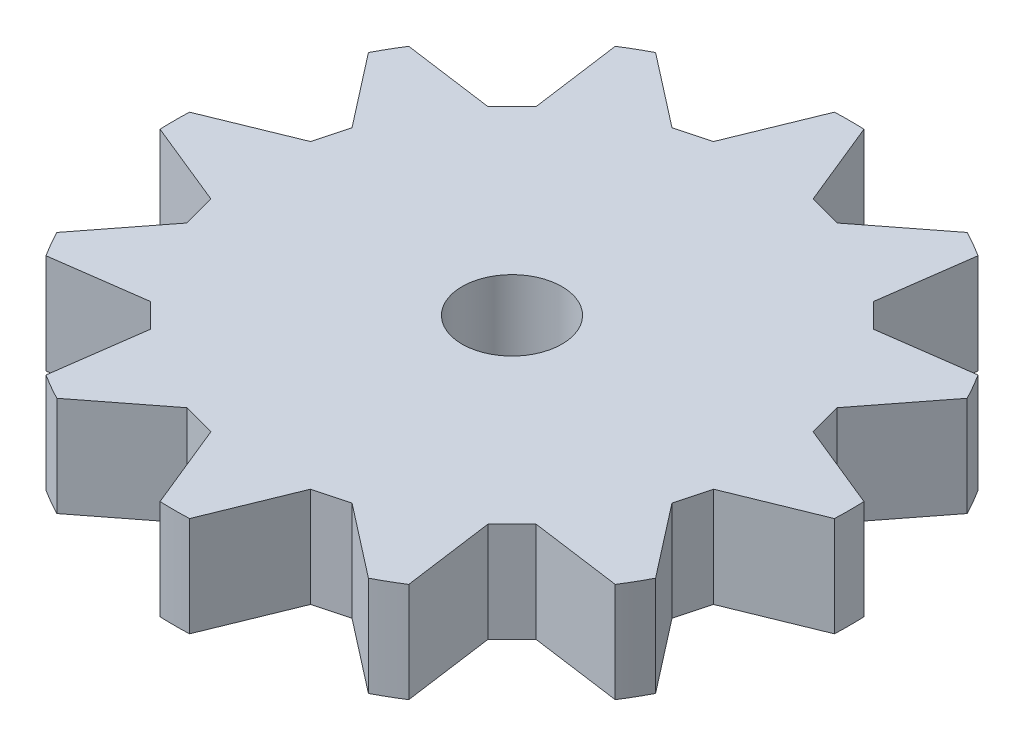
SolidWorks part; units mm, degrees
ref_plane "Front Plane" through (0, 0, 0) normal (0, 0, 1) x (1, 0, 0)
ref_plane "Top Plane" through (0, 0, 0) normal (0, 1, 0) x (1, 0, 0)
ref_plane "Right Plane" through (0, 0, 0) normal (1, 0, 0) x (0, 0, -1)
sketch "Sketch1" plane through (0, 0, 0) normal (0, 1, 0) x (1, 0, 0)
  circle A0 centre (0, 0) radius 15
  circle A1 centre (0, 0) radius 2.5
  dimension "D1" = 30
  dimension "D2" = 5
extrude "Boss-Extrude1" add sketch "Sketch1" along normal blind 5
sketch "Sketch2" plane through (0, 5, 0) normal (0, 1, 0) x (1, 0, 0)
  circle A3 centre (0, 0) radius 17
  circle A5 centre (0, 0) radius 15 construction
  circle M12 centre (0, 0) radius 2.5
  dimension "D1" = 2
extrude "Boss-Extrude2" add sketch "Sketch2" against normal up to surface (5 mm away) contours M12 | A3 region at (0, 5, 0) up to face at (0, 0, 15)
sketch "Sketch3" plane through (0, 5, 0) normal (0, 1, 0) x (1, 0, 0)
  line L0 (0, 0) -> (0, 17) construction
  line L1 (0.8001, 17) -> (-0.8001, 17)
  line L2 (-0.8001, 17) -> (-2.5659, 12.6675)
  line L3 (-2.5659, 12.6675) -> (-3.3388, 12.4604)
  line L4 (-9.6038, 14.0274) -> (6.2988, 15.79) construction
  line L5 (-1.8728, 16.8965) -> (-1.4211, 12.8215) construction
  line L6 (-3.3388, 12.4604) -> (0, 0) construction
  line L7 (2.5659, 12.6675) -> (3.3388, 12.4604)
  line L8 (0.8001, 17) -> (2.5659, 12.6675)
  line L9 (-0.8001, 17) -> (-0.8001, 18) construction
  line L10 (-0.8001, 18) -> (0, 18) construction
  line L11 (0, 18) -> (0, 17) construction
  line L12 (4.1116, 12.2534) -> (3.3388, 12.4604)
  line L13 (7.8071, 15.1225) -> (4.1116, 12.2534)
  line L14 (9.1929, 14.3224) -> (7.8071, 15.1225)
  line L15 (9.1929, 14.3224) -> (8.5559, 9.6874)
  line L16 (8.5559, 9.6874) -> (9.1217, 9.1217)
  line L17 (9.6874, 8.5559) -> (9.1217, 9.1217)
  line L18 (14.3224, 9.1929) -> (9.6874, 8.5559)
  line L19 (15.1225, 7.8071) -> (14.3224, 9.1929)
  line L20 (15.1225, 7.8071) -> (12.2534, 4.1116)
  line L21 (12.2534, 4.1116) -> (12.4604, 3.3388)
  line L22 (12.6675, 2.5659) -> (12.4604, 3.3388)
  line L23 (17, 0.8001) -> (12.6675, 2.5659)
  line L24 (17, -0.8001) -> (17, 0.8001)
  line L25 (17, -0.8001) -> (12.6675, -2.5659)
  line L26 (12.6675, -2.5659) -> (12.4604, -3.3388)
  line L27 (12.2534, -4.1116) -> (12.4604, -3.3388)
  line L28 (15.1225, -7.8071) -> (12.2534, -4.1116)
  line L29 (14.3224, -9.1929) -> (15.1225, -7.8071)
  line L30 (14.3224, -9.1929) -> (9.6874, -8.5559)
  line L31 (9.6874, -8.5559) -> (9.1217, -9.1217)
  line L32 (8.5559, -9.6874) -> (9.1217, -9.1217)
  line L33 (9.1929, -14.3224) -> (8.5559, -9.6874)
  line L34 (7.8071, -15.1225) -> (9.1929, -14.3224)
  line L35 (7.8071, -15.1225) -> (4.1116, -12.2534)
  line L36 (4.1116, -12.2534) -> (3.3388, -12.4604)
  line L37 (2.5659, -12.6675) -> (3.3388, -12.4604)
  line L38 (0.8001, -17) -> (2.5659, -12.6675)
  line L39 (-0.8001, -17) -> (0.8001, -17)
  line L40 (-0.8001, -17) -> (-2.5659, -12.6675)
  line L41 (-2.5659, -12.6675) -> (-3.3388, -12.4604)
  line L42 (-4.1116, -12.2534) -> (-3.3388, -12.4604)
  line L43 (-7.8071, -15.1225) -> (-4.1116, -12.2534)
  line L44 (-9.1929, -14.3224) -> (-7.8071, -15.1225)
  line L45 (-9.1929, -14.3224) -> (-8.5559, -9.6874)
  line L46 (-8.5559, -9.6874) -> (-9.1217, -9.1217)
  line L47 (-9.6874, -8.5559) -> (-9.1217, -9.1217)
  line L48 (-14.3224, -9.1929) -> (-9.6874, -8.5559)
  line L49 (-15.1225, -7.8071) -> (-14.3224, -9.1929)
  line L50 (-15.1225, -7.8071) -> (-12.2534, -4.1116)
  line L51 (-12.2534, -4.1116) -> (-12.4604, -3.3388)
  line L52 (-12.6675, -2.5659) -> (-12.4604, -3.3388)
  line L53 (-17, -0.8001) -> (-12.6675, -2.5659)
  line L54 (-17, 0.8001) -> (-17, -0.8001)
  line L55 (-17, 0.8001) -> (-12.6675, 2.5659)
  line L56 (-12.6675, 2.5659) -> (-12.4604, 3.3388)
  line L57 (-12.2534, 4.1116) -> (-12.4604, 3.3388)
  line L58 (-15.1225, 7.8071) -> (-12.2534, 4.1116)
  line L59 (-14.3224, 9.1929) -> (-15.1225, 7.8071)
  line L60 (-14.3224, 9.1929) -> (-9.6874, 8.5559)
  line L61 (-9.6874, 8.5559) -> (-9.1217, 9.1217)
  line L62 (-8.5559, 9.6874) -> (-9.1217, 9.1217)
  line L63 (-9.1929, 14.3224) -> (-8.5559, 9.6874)
  line L64 (-7.8071, 15.1225) -> (-9.1929, 14.3224)
  line L65 (-7.8071, 15.1225) -> (-4.1116, 12.2534)
  line L66 (-4.1116, 12.2534) -> (-3.3388, 12.4604)
  circle A0 centre (0, 0) radius 17 construction
  circle A1 centre (0, 0) radius 12.9 construction
  circle A2 centre (0, 0) radius 15 construction
  circle A3 centre (0, 0) radius 18
  point P12 (-1.6525, 14.9087)
  point P18 (0, 0)
  point P90 (0, 0)
  circle M14 centre (0, 0) radius 17
  dimension "D1" = 2
  dimension "D2" = 28.5
  dimension "2" = 2.1
  dimension "D3" = 15
  dimension "D4" = 1
  dimension "D5" = 12
extrude "Cut-Extrude1" cut sketch "Sketch3" along direction (0, 1, 0) on the side against the normal up to surface (5 mm away) contours L65 L66 L3 L2 M14 | L13 L8 L7 L12 M14 | L18 L15 L16 L17 M14 | L23 L20 L21 L22 M14 | L28 L25 L26 L27 M14 | L33 L30 L31 L32 M14 | L38 L35 L36 L37 M14 | L43 L40 L41 L42 M14 | L48 L45 L46 L47 M14 | L53 L50 L51 L52 M14 | L58 L55 L56 L57 M14 | L63 L60 L61 L62 M14 | A3 L64 L65 L2 L1 L8 L13 L14 L15 L18 L19 L20 L23 L24 L25 L28 L29 L30 L33 L34 L35 L38 L39 L40 L43 L44 L45 L48 L49 L50 L53 M14 region at (3.9641, 5, -14.7944) region at (-3.9641, 5, -14.7944) region at (10.8302, 5, -10.8302) region at (-10.8302, 5, -10.8302) region at (14.7944, 5, -3.9641) region at (-14.7944, 5, -3.9641) region at (14.7944, 5, 3.9641) region at (-14.7944, 5, 3.9641) region at (10.8302, 5, 10.8302) region at (-10.8302, 5, 10.8302) region at (3.9641, 5, 14.7944) region at (-3.9641, 5, 14.7944) region at (-17.4909, 5, 0) up to face at (0, 0, 2.5)
sketch "Sketch4" plane through (0, 5, 0) normal (0, 1, 0) x (1, 0, 0)
  line L41 (2.4921, 12.5838) -> (4.1337, 12.1439)
  line L42 (4.1337, 12.1439) -> (7.8015, 14.9915)
  line L43 (9.0823, 14.2521) -> (8.4501, 9.6518)
  line L44 (8.4501, 9.6518) -> (9.6518, 8.4501)
  line L45 (9.6518, 8.4501) -> (14.2521, 9.0823)
  line L46 (-7.852, 15.0308) -> (-4.1337, 12.1439)
  line L47 (2.4921, 12.5838) -> (4.0857, 12.1568)
  line L48 (0.7394, 16.8838) -> (2.4921, 12.5838)
  line L49 (-2.4921, 12.5838) -> (-0.7394, 16.8838)
  line L50 (-4.1337, 12.1439) -> (-2.4921, 12.5838)
  line L51 (-7.852, 15.0308) -> (-4.1337, 12.1439) construction
  line L52 (2.4921, 12.5838) -> (4.0857, 12.1568) construction
  line L53 (0.7394, 16.8838) -> (2.4921, 12.5838)
  line L54 (-2.4921, 12.5838) -> (-0.7394, 16.8838)
  line L55 (-4.1337, 12.1439) -> (-2.4921, 12.5838)
  line L56 (14.9915, 7.8015) -> (12.1439, 4.1337)
  line L57 (12.1439, 4.1337) -> (12.5838, 2.4921)
  line L58 (12.5838, 2.4921) -> (16.8838, 0.7394)
  line L59 (16.8838, -0.7394) -> (12.5838, -2.4921)
  line L60 (12.5838, -2.4921) -> (12.1439, -4.1337)
  line L61 (12.1439, -4.1337) -> (14.9915, -7.8015)
  line L62 (14.2521, -9.0823) -> (9.6518, -8.4501)
  line L63 (9.6518, -8.4501) -> (8.4501, -9.6518)
  line L64 (8.4501, -9.6518) -> (9.0823, -14.2521)
  line L65 (7.8015, -14.9915) -> (4.1337, -12.1439)
  line L66 (4.1337, -12.1439) -> (2.4921, -12.5838)
  line L67 (2.4921, -12.5838) -> (0.7394, -16.8838)
  line L68 (-0.7394, -16.8838) -> (-2.4921, -12.5838)
  line L69 (-2.4921, -12.5838) -> (-4.1337, -12.1439)
  line L70 (-4.1337, -12.1439) -> (-7.8015, -14.9915)
  line L71 (-9.0823, -14.2521) -> (-8.4501, -9.6518)
  line L72 (-8.4501, -9.6518) -> (-9.6518, -8.4501)
  line L73 (-9.6518, -8.4501) -> (-14.2521, -9.0823)
  line L74 (-14.9915, -7.8015) -> (-12.1439, -4.1337)
  line L75 (-12.1439, -4.1337) -> (-12.5838, -2.4921)
  line L76 (-12.5838, -2.4921) -> (-16.8838, -0.7394)
  line L77 (-16.8838, 0.7394) -> (-12.5838, 2.4921)
  line L78 (-12.5838, 2.4921) -> (-12.1439, 4.1337)
  line L79 (-12.1439, 4.1337) -> (-14.9915, 7.8015)
  line L80 (-14.2521, 9.0823) -> (-9.6518, 8.4501)
  line L81 (-9.6518, 8.4501) -> (-8.4501, 9.6518)
  line L82 (-8.4501, 9.6518) -> (-9.0823, 14.2521)
  line L83 (-7.8015, 14.9915) -> (-4.1337, 12.1439)
  arc A8 (9.0823, 14.2521) -> (7.8015, 14.9915) centre (0, 0) ccw
  arc A9 (0.7394, 16.8838) -> (-0.7394, 16.8838) centre (0, 0) ccw
  arc A10 (0.7394, 16.8838) -> (-0.7394, 16.8838) centre (0, 0) ccw
  arc A11 (14.9915, 7.8015) -> (14.2521, 9.0823) centre (0, 0) ccw
  arc A12 (16.8838, -0.7394) -> (16.8838, 0.7394) centre (0, 0) ccw
  arc A13 (14.2521, -9.0823) -> (14.9915, -7.8015) centre (0, 0) ccw
  arc A14 (7.8015, -14.9915) -> (9.0823, -14.2521) centre (0, 0) ccw
  arc A15 (-0.7394, -16.8838) -> (0.7394, -16.8838) centre (0, 0) ccw
  arc A16 (-9.0823, -14.2521) -> (-7.8015, -14.9915) centre (0, 0) ccw
  arc A17 (-14.9915, -7.8015) -> (-14.2521, -9.0823) centre (0, 0) ccw
  arc A18 (-16.8838, 0.7394) -> (-16.8838, -0.7394) centre (0, 0) ccw
  arc A19 (-14.2521, 9.0823) -> (-14.9915, 7.8015) centre (0, 0) ccw
  arc A20 (-7.8015, 14.9915) -> (-9.0823, 14.2521) centre (0, 0) ccw
  circle A21 centre (0, 0) radius 18.3542
  point P57 (0, 0)
  arc M8 (-7.7907, 15.1098) -> (-9.1901, 14.3018) centre (0, 0) ccw
  line M9 (-9.1901, 14.3018) -> (-8.5559, 9.6874)
  line M10 (-8.5559, 9.6874) -> (-9.6874, 8.5559)
  line M11 (-9.6874, 8.5559) -> (-14.3018, 9.1901)
  arc M12 (-14.3018, 9.1901) -> (-15.1098, 7.7907) centre (0, 0) ccw
  line M13 (-15.1098, 7.7907) -> (-12.2534, 4.1116)
  line M14 (-12.2534, 4.1116) -> (-12.6675, 2.5659)
  line M15 (-12.6675, 2.5659) -> (-16.9808, 0.8079)
  arc M16 (-16.9808, 0.8079) -> (-16.9808, -0.8079) centre (0, 0) ccw
  line M17 (-16.9808, -0.8079) -> (-12.6675, -2.5659)
  line M18 (-12.6675, -2.5659) -> (-12.2534, -4.1116)
  line M19 (-12.2534, -4.1116) -> (-15.1098, -7.7907)
  arc M20 (-15.1098, -7.7907) -> (-14.3018, -9.1901) centre (0, 0) ccw
  line M21 (-14.3018, -9.1901) -> (-9.6874, -8.5559)
  line M22 (-9.6874, -8.5559) -> (-8.5559, -9.6874)
  line M23 (-8.5559, -9.6874) -> (-9.1901, -14.3018)
  arc M24 (-9.1901, -14.3018) -> (-7.7907, -15.1098) centre (0, 0) ccw
  line M25 (-7.7907, -15.1098) -> (-4.1116, -12.2534)
  line M26 (-4.1116, -12.2534) -> (-2.5659, -12.6675)
  line M27 (-2.5659, -12.6675) -> (-0.8079, -16.9808)
  arc M28 (-0.8079, -16.9808) -> (0.8079, -16.9808) centre (0, 0) ccw
  line M29 (0.8079, -16.9808) -> (2.5659, -12.6675)
  line M30 (2.5659, -12.6675) -> (4.1116, -12.2534)
  line M31 (4.1116, -12.2534) -> (7.7907, -15.1098)
  arc M32 (7.7907, -15.1098) -> (9.1901, -14.3018) centre (0, 0) ccw
  line M33 (9.1901, -14.3018) -> (8.5559, -9.6874)
  line M34 (8.5559, -9.6874) -> (9.6874, -8.5559)
  line M35 (9.6874, -8.5559) -> (14.3018, -9.1901)
  arc M36 (14.3018, -9.1901) -> (15.1098, -7.7907) centre (0, 0) ccw
  line M37 (15.1098, -7.7907) -> (12.2534, -4.1116)
  line M38 (12.2534, -4.1116) -> (12.6675, -2.5659)
  line M39 (12.6675, -2.5659) -> (16.9808, -0.8079)
  arc M40 (16.9808, -0.8079) -> (16.9808, 0.8079) centre (0, 0) ccw
  line M41 (16.9808, 0.8079) -> (12.6675, 2.5659)
  line M42 (12.6675, 2.5659) -> (12.2534, 4.1116)
  line M43 (12.2534, 4.1116) -> (15.1098, 7.7907)
  arc M44 (15.1098, 7.7907) -> (14.3018, 9.1901) centre (0, 0) ccw
  line M45 (14.3018, 9.1901) -> (9.6874, 8.5559)
  line M46 (9.6874, 8.5559) -> (8.5559, 9.6874)
  line M47 (8.5559, 9.6874) -> (9.1901, 14.3018)
  arc M48 (9.1901, 14.3018) -> (7.7907, 15.1098) centre (0, 0) ccw
  line M49 (7.7907, 15.1098) -> (4.1116, 12.2534)
  line M50 (4.1116, 12.2534) -> (2.5659, 12.6675)
  line M51 (2.5659, 12.6675) -> (0.8079, 16.9808)
  arc M52 (0.8079, 16.9808) -> (-0.8079, 16.9808) centre (0, 0) ccw
  line M53 (-0.8079, 16.9808) -> (-2.5659, 12.6675)
  line M54 (-2.5659, 12.6675) -> (-4.1116, 12.2534)
  line M55 (-4.1116, 12.2534) -> (-7.7907, 15.1098)
  dimension "D1" = 0.1
extrude "Cut-Extrude2" cut sketch "Sketch4" against normal up to surface (5 mm away) contours A21 M8 M55 M54 M53 M52 M51 M50 M49 M48 M47 M46 M45 M44 M43 M42 M41 M40 M39 M38 M37 M36 M35 M34 M33 M32 M31 M30 M29 M28 M27 M26 M25 M24 M23 M22 M21 M20 M19 M18 M17 M16 M15 M14 M13 M12 M11 M10 M9 | A20 L83 M55 M8 M9 M10 M11 M12 M13 M14 M15 M16 M17 M18 M19 M20 M21 M22 M23 M24 M25 M26 M27 M28 M29 M30 M31 M32 M33 M34 M35 M36 M37 M38 M39 M40 M41 M42 M43 M44 M45 M46 M47 M48 M49 M50 M51 M52 M53 M54 region at (-17.8351, 5, 0) region at (-5.9806, 5, -13.6436) up to face at (0, 0, 2.5)
